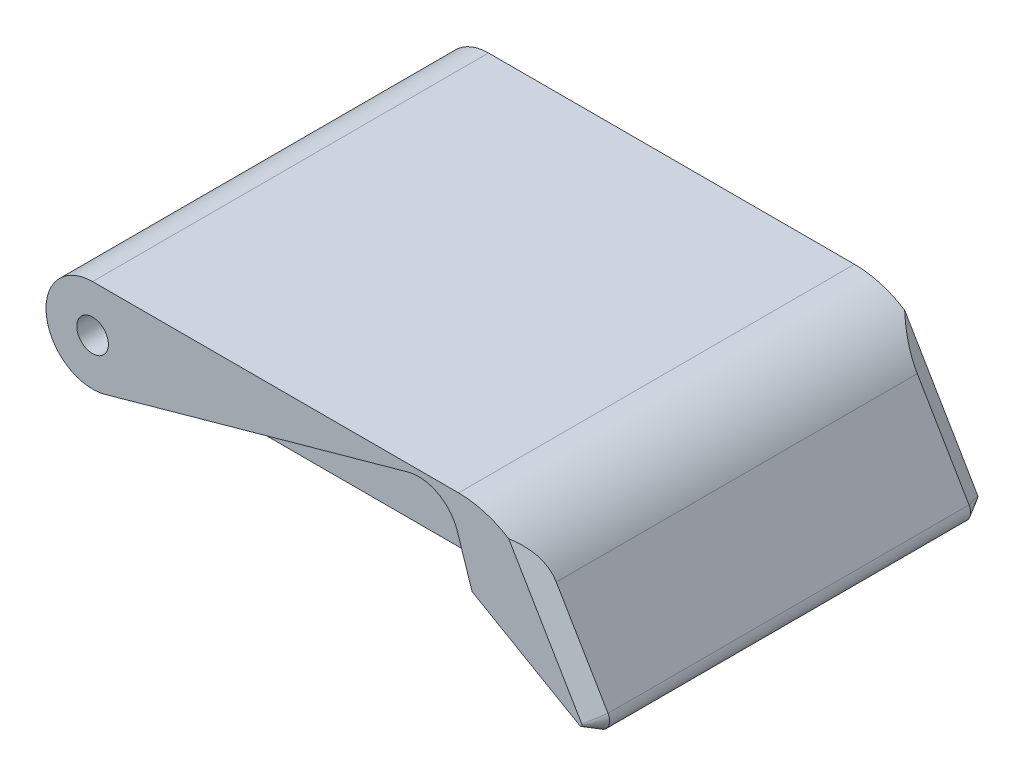
SolidWorks part; units mm, degrees
other "Markup1"
sketch "Sketch4" plane through (-6.35, -14.2625, 26.9875) normal (-0.881, -0.4145, 0.2283) x (0.285, -0.0796, 0.9552)
ref_plane "Front Plane" through (0, 0, 0) normal (0, 0, 1) x (1, 0, 0)
ref_plane "Top Plane" through (0, 0, 0) normal (0, 1, 0) x (1, 0, 0)
ref_plane "Right Plane" through (0, 0, 0) normal (1, 0, 0) x (0, 0, -1)
sketch "Sketch1" plane through (0, 0, 0) normal (0, 0, 1) x (1, 0, 0)
  line L0 (0, 6.35) -> (57.15, 6.35)
  line L3 (70.9475, -17.0656) -> (52.3875, -6.35)
  line L4 (52.3875, -6.35) -> (0, -6.35)
  line L5 (57.15, 6.35) -> (70.9475, -17.0656)
  arc A0 (0, 6.35) -> (0, -6.35) centre (0, 0) ccw
  dimension "D1" = 150
  dimension "D2" = 52.3875
  dimension "D4" = 21.4312
  dimension "D6" = 57.15
  dimension "D7" = 12.7
extrude "Boss-Extrude1" add sketch "Sketch1" along normal mid plane 53.975
sketch "Sketch2" plane through (0, 0, 26.9875) normal (0, 0, 1) x (1, 0, 0)
  line L1 (57.15, 6.35) -> (0, 6.35) construction
  circle A0 centre (0, 0) radius 2.159
  circle A1 centre (44.45, 0) radius 1.905
  dimension "D4" = 4.318
  dimension "D5" = 3.81
  dimension "D1" = 44.45
  dimension "D3" = 6.35
extrude "Cut-Extrude1" cut sketch "Sketch2" against normal through all
sketch "Sketch3" plane through (0, 0, 26.9875) normal (0, 0, 1) x (1, 0, 0)
  line L4 (1.7009, -6.118) -> (42.9617, 5.3532)
  line L7 (49.7281, 1.7359) -> (52.3875, -6.35)
  line L12 (0, -6.35) -> (52.3875, -6.35) construction
  line L13 (52.3875, -6.35) -> (0, -6.35)
  arc A4 (0, -6.35) -> (1.7009, -6.118) centre (0, 0) ccw
  arc A13 (49.7281, 1.7359) -> (42.9617, 5.3532) centre (44.45, 0) ccw
  dimension "D1" = 5.5563
extrude "Cut-Extrude2" cut sketch "Sketch3" against normal blind 6.35
mirror "Mirror1" about plane through (0, 0, 0) normal (0, 0, 1) of "Cut-Extrude2"
fillet "Fillet1" radius 1.5875 1 edges at (70.9475, -17.0656, 0)
chamfer "Chamfer2" distance 2.3811 angle 30 3 edges at (62.5177, -2.7596, 26.9875) (67.6453, -13.7926, 26.9875) (59.0558, -10.1999, 26.9875) first distance on face at (62.5177, -2.7596, 0) first distance on face at (67.225, -13.376, 0) first distance on face at (56.833, -8.9166, 0)
chamfer "Chamfer3" distance 2.3813 angle 30 3 edges at (62.5177, -2.7596, -26.9875) (67.6453, -13.7926, -26.9875) (59.0558, -10.1999, -26.9875) first distance on face at (62.5177, -2.7596, -1.1906) first distance on face at (67.225, -13.376, -1.1906) first distance on face at (56.833, -8.9166, -0.7937)
fillet "Fillet2" radius 12.7 1 edges at (57.15, 6.35, 0.0001)
